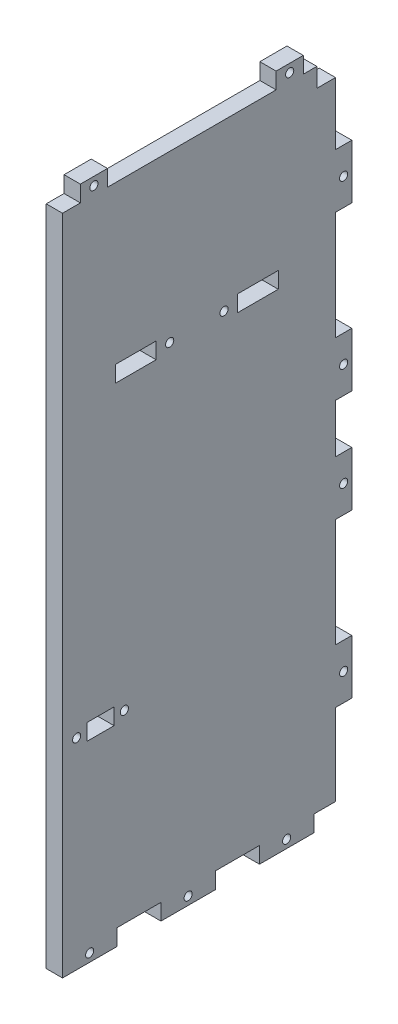
SolidWorks part; units mm, degrees
ref_plane "Plan de face" through (0, 0, 0) normal (0, 0, 1) x (1, 0, 0)
ref_plane "Plan de dessus" through (0, 0, 0) normal (0, 1, 0) x (1, 0, 0)
ref_plane "Plan de droite" through (0, 0, 0) normal (1, 0, 0) x (0, 0, -1)
sketch "Esquisse1" plane through (0, 0, 0) normal (1, 0, 0) x (0, 0, -1)
  line L0 (97.1531, 0) -> (-102.2664, 0) construction
  line L1 (-50.29, 119) -> (50.29, 119)
  line L2 (-50.29, 119) -> (-50.29, -119)
  line L3 (-50.29, -119) -> (50.29, -119)
  line L4 (50.29, 119) -> (50.29, -119)
  line L5 (0, 172.7153) -> (0, -236.1933) construction
  line L7 (-41.29, -48) -> (-31.29, -48)
  line L8 (-41.29, -48) -> (-41.29, -54)
  line L9 (-41.29, -54) -> (-31.29, -54)
  line L10 (-31.29, -48) -> (-31.29, -54)
  line L15 (-30.795, 61) -> (-15.795, 61)
  line L16 (-30.795, 61) -> (-30.795, 55)
  line L17 (-30.795, 55) -> (-15.795, 55)
  line L18 (-15.795, 61) -> (-15.795, 55)
  line L19 (14.205, 61) -> (29.205, 61)
  line L20 (14.205, 61) -> (14.205, 55)
  line L21 (14.205, 55) -> (29.205, 55)
  line L22 (29.205, 61) -> (29.205, 55)
  dimension "D1" = 238
  dimension "D2" = 100.58
  dimension "D4" = 119
  dimension "D13" = 15
  dimension "D14" = 15
  dimension "D15" = 30
  dimension "D16" = 6
  dimension "D17" = 6
  dimension "D3" = 50.29
  dimension "D5" = 58
  dimension "D6" = 19.495
  dimension "D7" = 9
  dimension "D8" = 167
  dimension "D9" = 6
  dimension "D10" = 10
extrude "Boss.-Extru.1" add sketch "Esquisse1" along normal blind 6
sketch "Esquisse3" plane through (6, 0, 0) normal (1, 0, 0) x (0, 0, -1)
  line L0 (-50.29, -119) -> (50.29, -119) construction
  line L1 (-50.29, -119) -> (-30.29, -119)
  line L2 (-50.29, -119) -> (-50.29, -125)
  line L3 (-50.29, -125) -> (-30.29, -125)
  line L4 (-30.29, -119) -> (-30.29, -125)
  line L5 (245.3741, 0) -> (-166.5298, 0) construction
  line L6 (50.29, -119) -> (50.29, 119) construction
  line L7 (22.29, -119) -> (42.29, -119)
  line L8 (22.29, -119) -> (22.29, -125)
  line L9 (22.29, -125) -> (42.29, -125)
  line L10 (0, 208.6671) -> (0, -232.3841) construction
  line L11 (-50.29, -119) -> (50.29, -119) construction
  line L12 (42.29, -119) -> (42.29, -125)
  line L13 (56.29, 29) -> (56.29, 9)
  line L14 (50.29, 9) -> (56.29, 9)
  line L15 (50.29, 29) -> (50.29, 9)
  line L16 (50.29, 29) -> (56.29, 29)
  line L17 (56.29, 89) -> (56.29, 69)
  line L18 (50.29, 69) -> (56.29, 69)
  line L19 (50.29, 89) -> (50.29, 69)
  line L20 (50.29, 89) -> (56.29, 89)
  line L21 (50.29, 119) -> (-50.29, 119) construction
  line L22 (50.29, -89) -> (56.29, -89)
  line L23 (50.29, -89) -> (50.29, -69)
  line L24 (50.29, -69) -> (56.29, -69)
  line L25 (56.29, -89) -> (56.29, -69)
  line L26 (50.29, -29) -> (56.29, -29)
  line L27 (50.29, -29) -> (50.29, -9)
  line L28 (50.29, -9) -> (56.29, -9)
  line L29 (0, -208.6671) -> (0, 232.3841) construction
  line L30 (-14, -119) -> (6, -119)
  line L31 (-14, -119) -> (-14, -125)
  line L32 (-14, -125) -> (6, -125)
  line L33 (6, -119) -> (6, -125)
  line L34 (50.29, -119) -> (50.29, 119) construction
  line L35 (56.29, -29) -> (56.29, -9)
  line L36 (38.41, 119) -> (28.41, 119)
  line L37 (38.41, 119) -> (38.41, 125)
  line L38 (38.41, 125) -> (28.41, 125)
  line L39 (28.41, 119) -> (28.41, 125)
  line L40 (-50.29, 119) -> (-50.29, -119) construction
  line L41 (-33.71, 119) -> (-43.71, 119)
  line L42 (-33.71, 119) -> (-33.71, 125)
  line L43 (-33.71, 125) -> (-43.71, 125)
  line L44 (-43.71, 119) -> (-43.71, 125)
  dimension "D2" = 20
  dimension "D3" = 6
  dimension "D4" = 20
  dimension "D5" = 8
  dimension "D6" = 6
  dimension "D7" = 6
  dimension "D8" = 20
  dimension "D9" = 6
  dimension "D10" = 20
  dimension "D11" = 6
  dimension "D12" = 20
  dimension "D13" = 16.29
  dimension "D14" = 30
  dimension "D15" = 40
  dimension "D16" = 6
  dimension "D17" = 10
  dimension "D18" = 11.88
  dimension "D19" = 6.58
  dimension "D20" = 10
  dimension "D21" = 6
  dimension "D22" = 16.29
extrude "Boss.-Extru.5" add sketch "Esquisse3" against normal blind 6
sketch "Esquisse7" plane through (0, 0, 0) normal (-1, 0, 0) x (0, 0, 1)
  line L1 (-50.29, 119) -> (-43.41, 119)
  line L2 (-50.29, 119) -> (-50.29, 112)
  line L3 (-50.29, 112) -> (-43.41, 112)
  line L4 (-43.41, 119) -> (-43.41, 112)
  dimension "D1" = 7
  dimension "D2" = 6.88
extrude "Enlèv. mat.-Extru.3" cut sketch "Esquisse7" against normal blind 6
sketch "Esquisse8" plane through (0, 0, 0) normal (-1, 0, 0) x (0, 0, 1)
  line L0 (-51.0214, 58) -> (44.3386, 58) construction
  line L1 (50.29, -125) -> (30.29, -125) construction
  line L2 (-14.205, 61) -> (-14.205, 55) construction
  line L3 (15.795, 55) -> (15.795, 61) construction
  line L4 (14, -119) -> (14, -125) construction
  line L5 (60.5401, -51) -> (10.4957, -51) construction
  line L6 (41.29, -48) -> (41.29, -54) construction
  line L7 (31.29, -54) -> (31.29, -48) construction
  line L8 (41.29, -54) -> (31.29, -54) construction
  line L9 (53.2872, 122) -> (-67.0711, 122) construction
  line L10 (33.71, 125) -> (43.71, 125) construction
  line L11 (-28.41, 125) -> (-28.41, 119) construction
  line L12 (33.71, 119) -> (33.71, 125) construction
  line L13 (-67.0711, -122) -> (72.8873, -122) construction
  line L16 (-22.29, -119) -> (-22.29, -125) construction
  line L17 (30.29, -125) -> (30.29, -119) construction
  line L18 (-53.29, 135.0788) -> (-53.29, -173.0788) construction
  line L19 (-56.29, 69) -> (-56.29, 89) construction
  line L21 (-56.29, -69) -> (-50.29, -69) construction
  line L22 (-50.29, 9) -> (-56.29, 9) construction
  line L23 (-56.29, 89) -> (-50.29, 89) construction
  circle A0 centre (4, -122) radius 1.5
  circle A1 centre (-9.205, 58) radius 1.5
  circle A2 centre (10.795, 58) radius 1.5
  circle A4 centre (27.5, -51) radius 1.5
  circle A5 centre (45.08, -51) radius 1.5
  circle A6 centre (38.71, 122) radius 1.5
  circle A7 centre (-33.41, 122) radius 1.5
  circle A8 centre (40.29, -122) radius 1.5
  circle A9 centre (-53.29, 79) radius 1.5
  circle A10 centre (-32.29, -122) radius 1.5
  circle A11 centre (-53.29, 19) radius 1.5
  circle A12 centre (-53.29, -79) radius 1.5
  circle A13 centre (-53.29, -19) radius 1.5
  dimension "D1" = 3
  dimension "D2" = 3
  dimension "D4" = 3
  dimension "D5" = 3
  dimension "D6" = 5
  dimension "D7" = 5
  dimension "D8" = 10
  dimension "D9" = 3
  dimension "D10" = 3
  dimension "D15" = 3
  dimension "D16" = 3
  dimension "D17" = 5
  dimension "D18" = 5
  dimension "D20" = 3
  dimension "D21" = 3
  dimension "D22" = 3
  dimension "D23" = 3
  dimension "D24" = 10
  dimension "D25" = 10
  dimension "D26" = 3
  dimension "D27" = 3
  dimension "D28" = 3
  dimension "D29" = 10
  dimension "D31" = 10
  dimension "D32" = 10
  dimension "D11" = 3.79
  dimension "D12" = 3.79
  dimension "D13" = 3
  dimension "D14" = 3
  dimension "D30" = 10
extrude "Enlèv. mat.-Extru.4" cut sketch "Esquisse8" against normal blind 6
equation "\"D3@Esquisse1\"=\"D2@Esquisse1\"/2"
equation "\"D4@Esquisse1\"=\"D1@Esquisse1\"/2"
